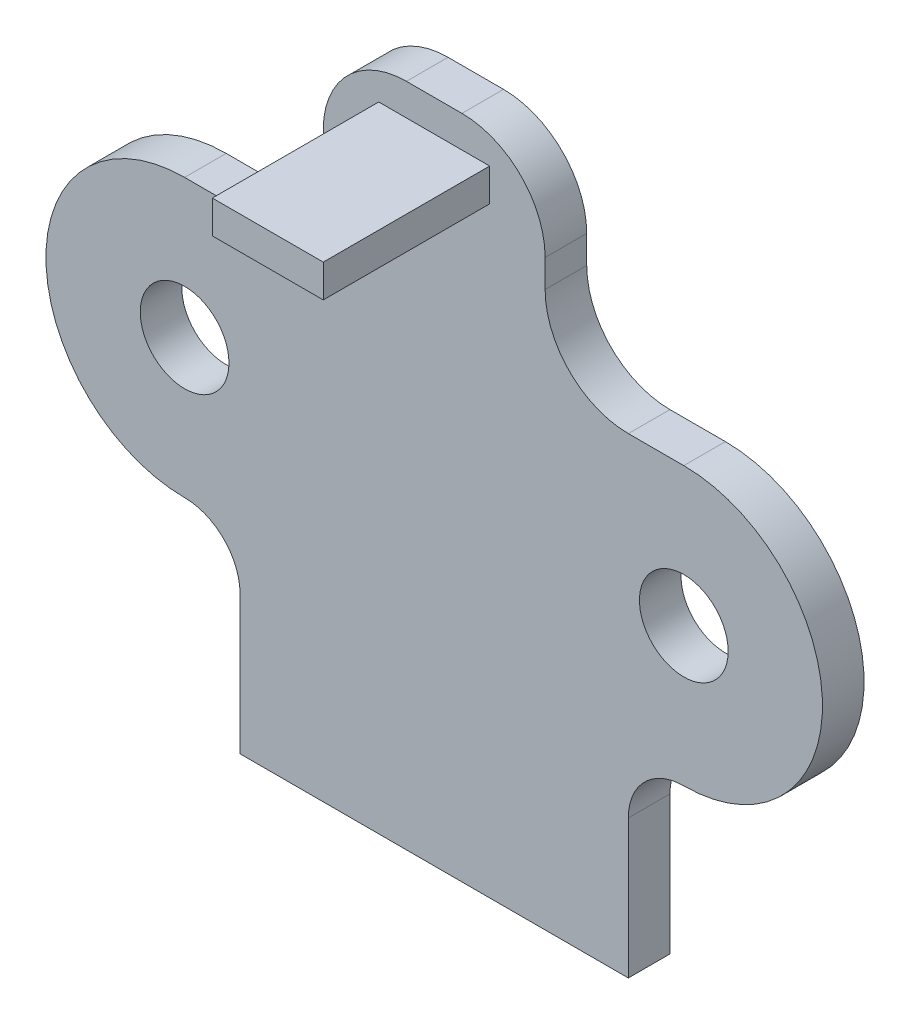
SolidWorks part; units mm, degrees
ref_plane "Front Plane" through (0, 0, 0) normal (0, 0, 1) x (1, 0, 0)
ref_plane "Top Plane" through (0, 0, 0) normal (0, 1, 0) x (1, 0, 0)
ref_plane "Right Plane" through (0, 0, 0) normal (1, 0, 0) x (0, 0, -1)
ref_plane "Plane1" through (0, 0, 1.5) normal (0, 0, 1) x (1, 0, 0)
sketch "Sketch1" plane through (0, 0, 1.5) normal (0, 0, 1) x (1, 0, 0)
  line L0 (-4, 9) -> (-4, 8)
  line L1 (-7, 5) -> (-9, 5)
  line L2 (-7, -7) -> (-7, -12)
  line L3 (-7, -12) -> (7, -12)
  line L4 (7, -12) -> (7, -7)
  line L5 (9, 5) -> (7, 5)
  line L6 (4, 8) -> (4, 9)
  line L7 (1, 12) -> (-1, 12)
  arc A0 (-4, 8) -> (-7, 5) centre (-7, 8) cw
  arc A1 (-9, 5) -> (-9, -5) centre (-9, 0) ccw
  arc A2 (-9, -5) -> (-7, -7) centre (-9, -7) cw
  arc A3 (7, -7) -> (9, -5) centre (9, -7) cw
  arc A4 (9, -5) -> (9, 5) centre (9, 0) ccw
  arc A5 (7, 5) -> (4, 8) centre (7, 8) cw
  arc A6 (4, 9) -> (1, 12) centre (1, 9) ccw
  arc A7 (-1, 12) -> (-4, 9) centre (-1, 9) ccw
extrude "Boss-Extrude1" add sketch "Sketch1" against normal blind 1.5
hole_wizard "Ø3.2 (3.2) Diameter Hole1" positions "Sketch3" profile "Sketch2" hole size "Ø3.2" standard "ANSI Metric"
sketch "Sketch3" plane through (0, 0, 1.5) normal (0, 0, 1) x (1, 0, 0)
  point P0 (-9, 0)
sketch "Sketch2" plane through (-9, 0, 1.5) normal (1, 0, 0) x (0, -1, 0)
  line L0 (0, 0) -> (0, 1.5)
  line L1 (0, 1.5) -> (1.6, 1.5)
  line L2 (1.6, 1.5) -> (1.6, 0)
  line L5 (1.6, 0) -> (0, 0)
  line L11 (0, -6.35) -> (0, 107.95) construction
  dimension "Thru Hole Dia." = 3.2
  dimension "Thru Hole Depth" = 1.5
mirror "Mirror1" about plane through (0, 0, 0) normal (1, 0, 0) of "Ø3.2 (3.2) Diameter Hole1"
sketch "Sketch5" plane through (0, 0, 1.5) normal (0, 0, 1) x (1, 0, 0)
  line L0 (2, 9.6738) -> (-2, 9.6738)
  line L1 (-2, 9.6738) -> (-2, 10.8554)
  line L2 (-2, 10.8554) -> (2, 10.8554)
  line L3 (2, 10.8554) -> (2, 9.6738)
extrude "Boss-Extrude2" add sketch "Sketch5" along normal blind 6
ref_axis "Axis1" through (-9, 0, 0) along (0, 0, 1)
ref_axis "Axis2" through (9, 0, 0) along (0, 0, 1)
